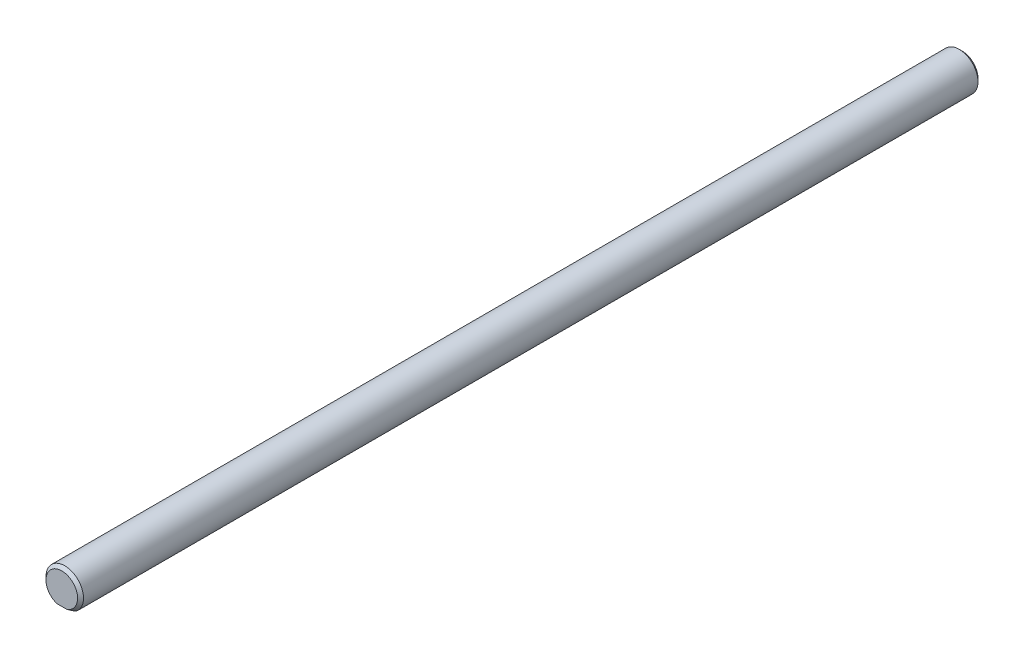
SolidWorks part; units mm, degrees
ref_plane "Front" through (0, 0, 0) normal (0, 0, 1) x (1, 0, 0)
ref_plane "Top" through (0, 0, 0) normal (0, 1, 0) x (1, 0, 0)
ref_plane "Right" through (0, 0, 0) normal (1, 0, 0) x (0, 0, -1)
sketch "Sketch1" plane through (0, 0, 0) normal (0, 0, 1) x (1, 0, 0)
  line L0 (-1.905, -2.54) -> (1.905, -2.54)
  circle A0 centre (0, 0) radius 3.175 construction
  arc A1 (-1.905, -2.54) -> (1.905, -2.54) centre (0, 0) cw
  dimension "D1" = 6.35
  dimension "D2" = 5.715
sketch "Sketch2" plane through (0, 0, 0) normal (0, 1, 0) x (1, 0, 0)
  line L0 (0, -76.2) -> (0, 76.2)
  point P3 (0, 0)
  dimension "D1" = 152.4
sweep "Sweep1" add profiles "Sketch1" path "Sketch2"
chamfer "Chamfer1" distance 0.5 angle 45 2 edges at (0, 3.175, -76.2) (0, 3.175, 76.2)
ref_axis "Axis1" through (0, 0, -75.7) along (0, 0, 1)
